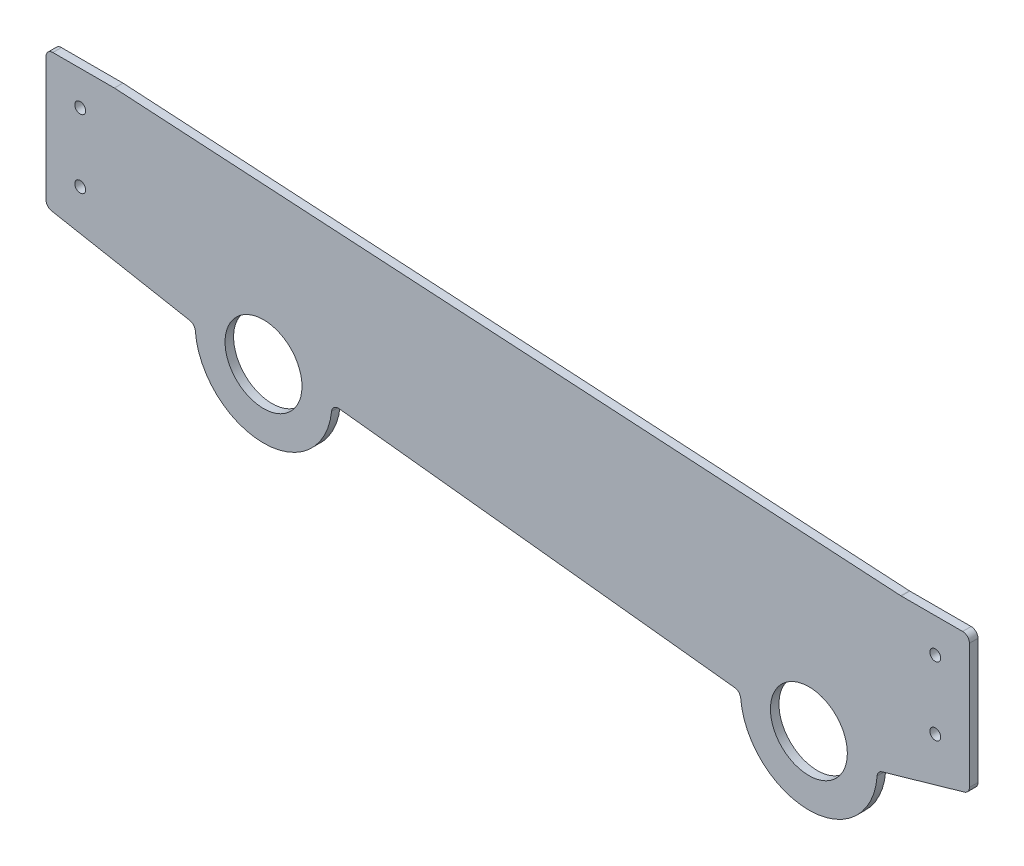
SolidWorks part; units mm, degrees
ref_plane "Front Plane" through (0, 0, 0) normal (0, 0, 1) x (1, 0, 0)
ref_plane "Top Plane" through (0, 0, 0) normal (0, 1, 0) x (1, 0, 0)
ref_plane "Right Plane" through (0, 0, 0) normal (1, 0, 0) x (0, 0, -1)
sketch "Sketch1" plane through (0, 0, 0) normal (0, 0, 1) x (1, 0, 0)
  line L0 (-101.6, -38.1991) -> (158.75, -38.1991) construction
  line L1 (-101.6, 76.1009) -> (273.6285, 76.1009) construction
  line L2 (-101.6, 164.2389) -> (101.6, 164.2389) construction
  line L3 (0, -88.9) -> (0, 235.6129) construction
  line L6 (-146.05, 113.4389) -> (-171.45, 113.4389) construction
  line L7 (-146.05, 113.4389) -> (-146.05, 164.2389) construction
  line L8 (-146.05, 164.2389) -> (-171.45, 164.2389)
  line L9 (-171.45, 113.4389) -> (-171.45, 164.2389)
  line L10 (-146.05, 113.4389) -> (-171.45, 164.2389) construction
  line L11 (-146.05, 164.2389) -> (-171.45, 113.4389) construction
  line L12 (-146.05, 164.2389) -> (146.05, 146.9669)
  line L17 (146.05, 96.1669) -> (171.45, 96.1669) construction
  line L18 (146.05, 96.1669) -> (146.05, 146.9669) construction
  line L19 (146.05, 146.9669) -> (171.45, 146.9669)
  line L20 (171.45, 96.1669) -> (171.45, 146.9669)
  line L21 (146.05, 96.1669) -> (171.45, 146.9669) construction
  line L22 (146.05, 146.9669) -> (171.45, 96.1669) construction
  line L23 (-146.05, 164.2389) -> (146.05, 146.9669)
  line L24 (-171.45, 113.4389) -> (-116.0814, 103.1319)
  line L25 (-65.2814, 103.1319) -> (86.4249, 86.356)
  line L26 (137.2249, 86.356) -> (171.45, 96.1669)
  circle A3 centre (0, 0) radius 88.9 construction
  circle A4 centre (111.8249, 86.356) radius 52.3875 construction
  circle A5 centre (-90.6814, 103.1319) radius 25.4 construction
  circle A6 centre (0, 172.7119) radius 88.9 construction
  circle A7 centre (-90.6814, 103.1319) radius 14.2875
  circle A8 centre (111.8249, 86.356) radius 14.2875
  circle A11 centre (-158.75, 151.5389) radius 2.0193
  circle A12 centre (158.75, 134.2669) radius 2.0193
  circle A13 centre (-90.6814, 103.1319) radius 23.495 construction
  circle A14 centre (111.8249, 86.356) radius 23.495 construction
  circle A15 centre (158.75, 108.8669) radius 2.0193
  circle A16 centre (-158.75, 126.1389) radius 2.0193
  arc A17 (-116.0814, 103.1319) -> (-65.2814, 103.1319) centre (-90.6814, 103.1319) ccw
  arc A18 (86.4249, 86.356) -> (137.2249, 86.356) centre (111.8249, 86.356) ccw
  point P12 (0, 164.2389)
  point P24 (-158.75, 151.5389)
  point P25 (158.75, 134.2669)
  point P37 (158.75, 121.5669)
  point P38 (5.3981, 114.787)
  point P39 (158.75, 121.5669)
  point P46 (158.75, 146.9669)
  point P48 (-158.75, 138.8389)
  dimension "D1" = 177.8
  dimension "D2" = 104.775
  dimension "D3" = 38.1991
  dimension "D5" = 50.8
  dimension "D10" = 177.8
  dimension "D12" = 28.575
  dimension "D13" = 28.575
  dimension "D14" = 4.0386
  dimension "D18" = 4.0386
  dimension "D19" = 46.99
  dimension "D20" = 46.99
  dimension "D32" = 25.4
  dimension "D33" = 25.4
  dimension "D4" = 114.3
  dimension "D6" = 203.2
  dimension "D7" = 158.75
  dimension "D8" = 203.2
  dimension "D9" = 202.438
  dimension "D11" = 260.35
  dimension "D15" = 189.738
  dimension "D16" = 317.5
  dimension "D17" = 172.466
  dimension "D22" = 12.7
  dimension "D23" = 25.4
  dimension "D24" = 12.7
  dimension "D25" = 12.7
  dimension "D26" = 25.4
  dimension "D27" = 71.374
  dimension "D28" = 50.8
  dimension "D29" = 50.8
  dimension "D30" = 12.7
  dimension "D31" = 61.107
  dimension "D21" = 2
extrude "Boss-Extrude1" add sketch "Sketch1" along normal blind 3.175 contours L20 L19 L12 L8 L9 A16 A15 A12 A11 A8 A7 region at (2.9498, 123.6895, 0)
fillet "Fillet1" radius 2.54 9 edges at (-171.45, 164.2389, 1.5875) (171.45, 146.9669, 1.5875) (171.45, 96.1669, 1.5875) (-171.45, 113.4389, 1.5875) (146.05, 146.9669, 1.5875) (86.4249, 86.356, 1.5875) (137.2249, 86.356, 1.5875) (-65.2814, 103.1319, 1.5875) (-116.0814, 103.1319, 1.5875)
